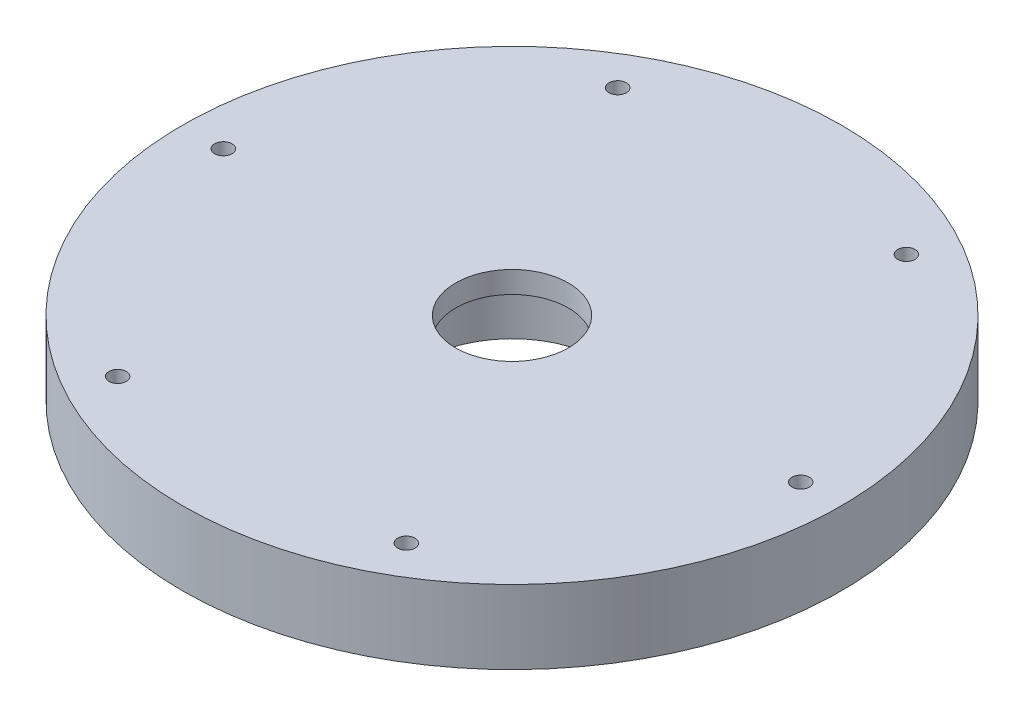
SolidWorks part; units mm, degrees
material "1060 Alloy"
ref_plane "Front Plane" through (0, 0, 0) normal (0, 0, 1) x (1, 0, 0)
ref_plane "Top Plane" through (0, 0, 0) normal (0, 1, 0) x (1, 0, 0)
ref_plane "Right Plane" through (0, 0, 0) normal (1, 0, 0) x (0, 0, -1)
sketch "Sketch1" plane through (0, 0, 0) normal (0, 0, 1) x (1, 0, 0)
  line L0 (0, 38.7087) -> (0, -19.5852) construction
  line L1 (-6.5, 0) -> (-38, 0)
  line L2 (-38, 0) -> (-38, -8.5)
  line L4 (-10.5, -9.75) -> (-10.5, -2.5)
  line L5 (-10.5, -2.5) -> (-6.5, -2.5)
  line L6 (-6.5, -2.5) -> (-6.5, 0)
  line L7 (-10.5, -9.75) -> (-35, -9.75)
  line L8 (-35, -9.75) -> (-35, -8.5)
  line L9 (-35, -8.5) -> (-38, -8.5)
  dimension "D1" = 6.5
  dimension "D2" = 10.5
  dimension "D4" = 38
  dimension "D5" = 3
  dimension "D6" = 1.25
  dimension "D7" = 2.5
  dimension "D3" = 6
revolve "Revolve1" add sketch "Sketch1" angle 360 about L0
sketch "Sketch2" plane through (0, -9.75, 0) normal (0, -1, 0) x (1, 0, 0)
  circle A0 centre (0, 0) radius 33.2875 construction
  circle A1 centre (-33.2875, 0) radius 1
  circle A2 centre (-16.6438, 28.8278) radius 1
  circle A3 centre (16.6437, 28.8278) radius 1
  circle A4 centre (33.2875, 0) radius 1
  circle A5 centre (16.6438, -28.8278) radius 1
  circle A6 centre (-16.6437, -28.8278) radius 1
  point P17 (0, 0)
  dimension "D1" = 2
  dimension "D3" = 66.575
  dimension "D2" = 6
extrude "Cut-Extrude1" cut sketch "Sketch2" against normal through all
equation "\"Stator_OD\"= 60'No Tolerance given"
equation "\"A\"=35.81 'taken off spec sheet for 06808 (A)"
equation "\"Rotor_ID\"= 30'No Tolerance Given"
equation "\"back_bearing_Thickness\"= 5'-0.12"
equation "\"back_bearing_OD\"= 24'-0.009 https://www.mcmaster.com/5972K155/"
equation "\"Stator_Gap\"= 0.0375'+- 0.0125 (From 1.3.3.1 Kollmorgen manual)"
equation "\"Back_mount_hole\"= 1.75'To be tapped to M2 (USE LOCKTITE)"
equation "\"facePlate_Mount_Hole\"= 2.75'To be tapped to M3"
equation "\"back_bearing_ID\"= 15'"
equation "\"final_shaftD\"= 12'To fit in harmonic"
equation "\"final_shaftL\"= 50'random length. Idk"
equation "\"back_bearing_IDOD\"= 16.5'measured off CAD, actually 16.75, but rounded down to nicer number"
equation "\"rotor_shaftD\"= \"Rotor_ID\" - (\"rotor-shaft_gap\")*2'"
equation "\"front_bearing_ID\"= 12'https://www.mcmaster.com/5972K154/"
equation "\"front_bearing_OD\"= 21'-0.009"
equation "\"front_bearing_IDOD\"= 13.5'Measured off CAD. Actually 13.75, but rounded down"
equation "\"front_bearing_Thickness\"= 5'-0.12"
equation "\"rotor_thickness\"= 2.4'measured off CAD"
equation "\"rotor_height\"= 32.86'+-0.075 taken off spec sheet for 06826 (C)"
equation "\"D1@Sketch1\"=\"final_shaftD\"/2+0.5"
equation "\"D2@Sketch1\"=\"front_bearing_OD\"/2"
equation "\"D4@Sketch1\"=\"Stator_OD\"/2+8"
equation "\"D3@Sketch1\"=\"front_bearing_Thickness\"+1"
equation "\"D3@Sketch2\"= \"Stator_OD\" + \"Stator_Gap\" * 2 + 6.5"
equation "\"D1@Sketch2\"=\"Back_mount_hole\"+0.25"
